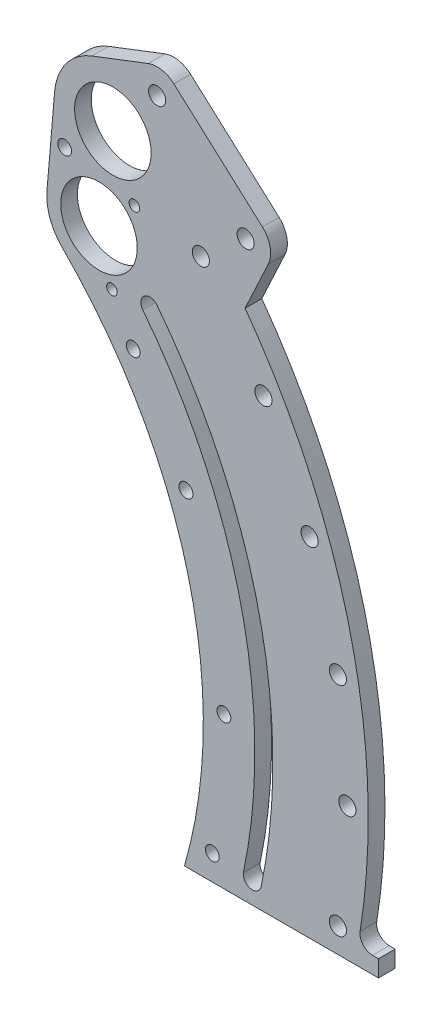
SolidWorks part; units mm, degrees
material "6061-T6 (SS)"
ref_plane "Front Plane" through (0, 0, 0) normal (0, 0, 1) x (1, 0, 0)
ref_plane "Top Plane" through (0, 0, 0) normal (0, 1, 0) x (1, 0, 0)
ref_plane "Right Plane" through (0, 0, 0) normal (1, 0, 0) x (0, 0, -1)
sketch "Sketch1" plane through (0, 0, 0) normal (0, 0, 1) x (1, 0, 0)
  line L0 (0, 0) -> (177.8, 0) construction
  line L1 (177.8, 0) -> (183.3563, 0) construction
  line L2 (0, 0) -> (191.1772, 6.6761) construction
  line L3 (0, 0) -> (182.7798, 182.7798) construction
  line L4 (184.7031, 10.1184) -> (184.959, 2.7905) construction
  line L5 (184.959, 2.7905) -> (191.4331, -0.6518) construction
  line L6 (191.4331, -0.6518) -> (197.6513, 3.2337) construction
  line L7 (197.6513, 3.2337) -> (197.3954, 10.5616) construction
  line L8 (197.3954, 10.5616) -> (190.9213, 14.0039) construction
  line L9 (190.9213, 14.0039) -> (184.7031, 10.1184) construction
  line L10 (156.6987, 109.7216) -> (0, 0) construction
  line L11 (0, 0) -> (176.7324, 73.2049) construction
  line L12 (183.3563, 0) -> (183.3563, -50.8) construction
  line L13 (176.1785, -50.8) -> (183.3563, -50.8) construction
  line L14 (0, 0) -> (186.7878, -41.275) construction
  line L15 (0, 0) -> (203.2, 0) construction
  line L16 (203.2, 0) -> (209.55, 0) construction
  line L17 (209.55, 0) -> (228.6, 0) construction
  line L18 (228.6, 0) -> (238.125, 0) construction
  line L19 (0, 0) -> (238.125, 0) construction
  line L20 (0, 0) -> (234.5073, 41.35) construction
  line L21 (176.1785, -50.8) -> (240.7615, -50.8)
  line L22 (0, 0) -> (238.125, 0) construction
  line L23 (0, 0) -> (234.5073, -41.35) construction
  line L24 (129.6524, 129.6524) -> (173.9925, 173.9925)
  line L25 (165.5338, 128.4903) -> (160.5177, 124.5966) construction
  line L26 (198.8628, -41.7593) -> (205.1195, -42.8625) construction
  arc A0 (183.3563, 0) -> (129.6524, 129.6524) centre (0, 0) ccw
  arc A1 (184.9438, 0) -> (130.775, 130.775) centre (0, 0) ccw construction
  circle A3 centre (191.1772, 6.6761) radius 6.35 construction
  circle A4 centre (191.1772, 6.6761) radius 2.6289
  circle A5 centre (156.6987, 109.7216) radius 2.6289
  circle A6 centre (176.7324, 73.2049) radius 2.667
  arc A7 (183.3563, 0) -> (176.1785, -50.8) centre (0, 0) cw
  circle A8 centre (186.7878, -41.275) radius 2.6289
  arc A9 (203.2, 0) -> (143.6841, 143.6841) centre (0, 0) ccw construction
  arc A10 (209.55, 0) -> (148.1742, 148.1742) centre (0, 0) ccw construction
  arc A11 (228.6, 0) -> (161.6446, 161.6446) centre (0, 0) ccw construction
  arc A12 (238.125, 0) -> (168.3798, 168.3798) centre (0, 0) ccw construction
  circle A13 centre (238.125, 0) radius 3.2639
  circle A14 centre (234.5073, 41.35) radius 3.2639
  circle A15 centre (223.7643, 81.4435) radius 3.2639
  circle A16 centre (206.2223, 119.0625) radius 3.2639
  circle A17 centre (182.4143, 153.0638) radius 3.2639
  arc A18 (240.7615, -50.8) -> (173.9925, 173.9925) centre (0, 0) ccw
  circle A19 centre (234.5073, -41.35) radius 3.2639
  arc A20 (209.55, 0) -> (165.5338, 128.4903) centre (0, 0) ccw construction
  arc A21 (160.5177, 124.5966) -> (203.2, 0) centre (0, 0) cw construction
  arc A22 (209.55, 0) -> (205.1195, -42.8625) centre (0, 0) cw construction
  arc A23 (203.2, 0) -> (198.8628, -41.7593) centre (0, 0) cw construction
  arc A24 (165.5338, 128.4903) -> (160.5177, 124.5966) centre (163.0257, 126.5435) ccw construction
  arc A25 (205.1195, -42.8625) -> (198.8628, -41.7593) centre (201.9911, -42.3109) cw construction
  arc A26 (202.946, 0) -> (198.6134, -41.711) centre (0, 0) cw
  arc A27 (205.3689, -42.9106) -> (198.6134, -41.711) centre (201.9911, -42.3109) cw
  arc A28 (209.804, 0) -> (205.3689, -42.9106) centre (0, 0) cw
  arc A29 (209.804, 0) -> (165.7345, 128.646) centre (0, 0) ccw
  arc A30 (165.7345, 128.646) -> (160.317, 124.4409) centre (163.0257, 126.5435) ccw
  arc A31 (160.317, 124.4409) -> (202.946, 0) centre (0, 0) cw
  point P9 (151.4971, 106.0794)
  point P20 (170.8657, 70.7749)
  point P27 (179.0372, -39.5623)
  dimension "D3" = 1.5875
  dimension "D4" = 12.7
  dimension "D6" = 5.2578
  dimension "D8" = 5.2578
  dimension "D12" = 5.334
  dimension "D14" = 50.8
  dimension "D15" = 5.2578
  dimension "D19" = 6.35
  dimension "D20" = 19.05
  dimension "D22" = 6.5278
  dimension "D26" = 7.9375
  dimension "D30" = 25.4
  dimension "D31" = 7.9375
  dimension "D33" = 183.3562
  dimension "D1" = 177.8
  dimension "D2" = 5.5562
  dimension "D5" = 2
  dimension "D7" = 45
  dimension "D9" = 6.35
  dimension "D10" = 10
  dimension "D11" = 22.5
  dimension "D13" = 6.35
  dimension "D16" = 9.525
  dimension "D17" = 7.9375
  dimension "D18" = 203.2
  dimension "D21" = 9.525
  dimension "D24" = 10
  dimension "D25" = 238.125
  dimension "D28" = 10
  dimension "D29" = 238.125
  dimension "D32" = 0.254
  dimension "D23" = 5
  dimension "D27" = 2
extrude "Boss-Extrude1" add sketch "Sketch1" along normal blind 6.35 contours L21 A18 L24 A0 A7 A19 A4 A5 A6 A8 A13 A14 A15 A16 A17 A22 A25 A23 A21 A24 A20 region at (184.0595, -26.0065, 0)
sketch "Sketch2" plane through (0, 0, 6.35) normal (0, 0, 1) x (1, 0, 0)
  line L0 (0, 0) -> (125.7236, 125.7236) construction
  line L1 (0, 0) -> (183.3562, 0) construction
  line L2 (125.7236, 125.7236) -> (143.6841, 143.6841) construction
  line L3 (129.6524, 129.6524) -> (173.9925, 173.9925) construction
  line L4 (143.6841, 143.6841) -> (148.964, 177.5652) construction
  line L6 (0, 0) -> (148.964, 177.5652) construction
  arc A0 (176.1785, -50.8) -> (129.6524, 129.6524) centre (0, 0) ccw construction
  circle A1 centre (143.6841, 143.6841) radius 14.5542
  circle A2 centre (143.6841, 143.6841) radius 25.4 construction
  circle A3 centre (143.6841, 143.6841) radius 11.43 construction
  circle A4 centre (143.6841, 143.6841) radius 19.05 construction
  circle A5 centre (148.964, 177.5652) radius 22.86 construction
  circle A6 centre (148.964, 177.5652) radius 14.5542
  dimension "D4" = 29.1084
  dimension "D5" = 50.8
  dimension "D6" = 22.86
  dimension "D7" = 38.1
  dimension "D8" = 45.72
  dimension "D9" = 231.775
  dimension "D10" = 29.1084
  dimension "D1" = 177.8
  dimension "D2" = 45
  dimension "D3" = 25.4
  dimension "D11" = 34.29
sketch "Sketch3" plane through (0, 0, 6.35) normal (0, 0, 1) x (1, 0, 0)
  line L0 (129.6524, 129.6524) -> (173.9925, 173.9925) construction
  line L1 (129.6524, 129.6524) -> (161.6446, 161.6446)
  line L4 (123.9121, 145.3706) -> (126.8194, 179.454)
  line L5 (161.6446, 161.6446) -> (173.9925, 173.9925)
  line L6 (0, 0) -> (199.4397, 167.3498) construction
  line L7 (0, 0) -> (183.3562, 0) construction
  line L9 (208.0723, 163.3243) -> (199.2435, 144.391)
  line L10 (148.964, 177.5652) -> (165.7989, 197.6325) construction
  line L11 (0, 0) -> (148.964, 177.5652) construction
  line L12 (140.998, 198.3135) -> (162.385, 206.5246)
  line L13 (172.1715, 204.7117) -> (205.8123, 174.429)
  line L14 (143.6841, 143.6841) -> (148.964, 177.5652) construction
  line L15 (146.324, 160.6246) -> (130.6383, 163.069) construction
  arc A1 (129.6524, 129.6524) -> (123.9121, 145.3706) centre (143.6841, 143.6841) cw
  arc A2 (140.998, 198.3135) -> (126.8194, 179.454) centre (148.964, 177.5652) ccw
  circle A3 centre (148.964, 177.5652) radius 14.5542
  circle A4 centre (199.4397, 167.3498) radius 3.2639
  arc A5 (208.0723, 163.3243) -> (205.8123, 174.429) centre (199.4397, 167.3498) ccw
  arc A7 (173.9925, 173.9925) -> (199.2435, 144.391) centre (0, 0) cw
  arc A8 (240.7615, -50.8) -> (173.9925, 173.9925) centre (0, 0) ccw construction
  circle A9 centre (165.7989, 197.6325) radius 9.525 construction
  circle A10 centre (148.964, 177.5652) radius 16.1417 construction
  circle A11 centre (165.7989, 197.6325) radius 3.2639
  arc A12 (162.385, 206.5246) -> (172.1715, 204.7117) centre (165.7989, 197.6325) cw
  circle A13 centre (130.6383, 163.069) radius 2.6289
  circle A14 centre (130.6383, 163.069) radius 3.9687 construction
  dimension "D1" = 25.4
  dimension "D2" = 29.1084
  dimension "D3" = 22.225
  dimension "D5" = 260.35
  dimension "D6" = 6.5278
  dimension "D7" = 9.525
  dimension "D8" = 25
  dimension "D9" = 19.05
  dimension "D10" = 1.5875
  dimension "D11" = 6.5278
  dimension "D12" = 9.525
  dimension "D14" = 5.2578
  dimension "D15" = 7.9375
  dimension "D4" = 40
  dimension "D13" = 26.1937
  dimension "D16" = 15.875
extrude "Boss-Extrude2" add sketch "Sketch3" against normal blind 6.35
sketch "Sketch4" plane through (0, 0, 6.35) normal (0, 0, 1) x (1, 0, 0)
  line L0 (143.6841, 143.6841) -> (157.1545, 157.1545) construction
  line L1 (125.7236, 125.7236) -> (143.6841, 143.6841) construction
  line L2 (143.6841, 143.6841) -> (148.6146, 125.2832) construction
  circle A0 centre (143.6841, 143.6841) radius 14.5542
  circle A1 centre (157.1545, 157.1545) radius 2.0193
  circle A2 centre (148.6146, 125.2832) radius 2.0193
  dimension "D1" = 29.1084
  dimension "D2" = 4.0386
  dimension "D4" = 4.0386
  dimension "D3" = 19.05
  dimension "D5" = 19.05
  dimension "D6" = 60
extrude "Cut-Extrude1" cut sketch "Sketch4" against normal through all
sketch "Sketch5" plane through (0, 0, 6.35) normal (0, 0, 1) x (1, 0, 0)
  line L0 (240.7615, -50.8) -> (249.9519, -50.8)
  line L1 (249.9519, -50.8) -> (249.9519, -44.45)
  line L2 (249.9519, -44.45) -> (242.0144, -44.45)
  arc A0 (240.7615, -50.8) -> (199.2435, 144.391) centre (0, 0) ccw construction
  arc A1 (242.9628, -38.9339) -> (199.2435, 144.391) centre (0, 0) ccw construction
  arc A2 (242.0144, -44.45) -> (242.9628, -38.9339) centre (0, 0) ccw construction
  arc A3 (240.7615, -50.8) -> (242.0144, -44.45) centre (0, 0) ccw
  point P3 (0, 0)
  point P6 (242.0144, -44.45)
  dimension "D2" = 6.35
  dimension "D3" = 7.9375
extrude "Boss-Extrude3" add sketch "Sketch5" against normal blind 6.35
fillet "Fillet1" radius 4.7625 1 edges at (242.0144, -44.45, 3.175)
